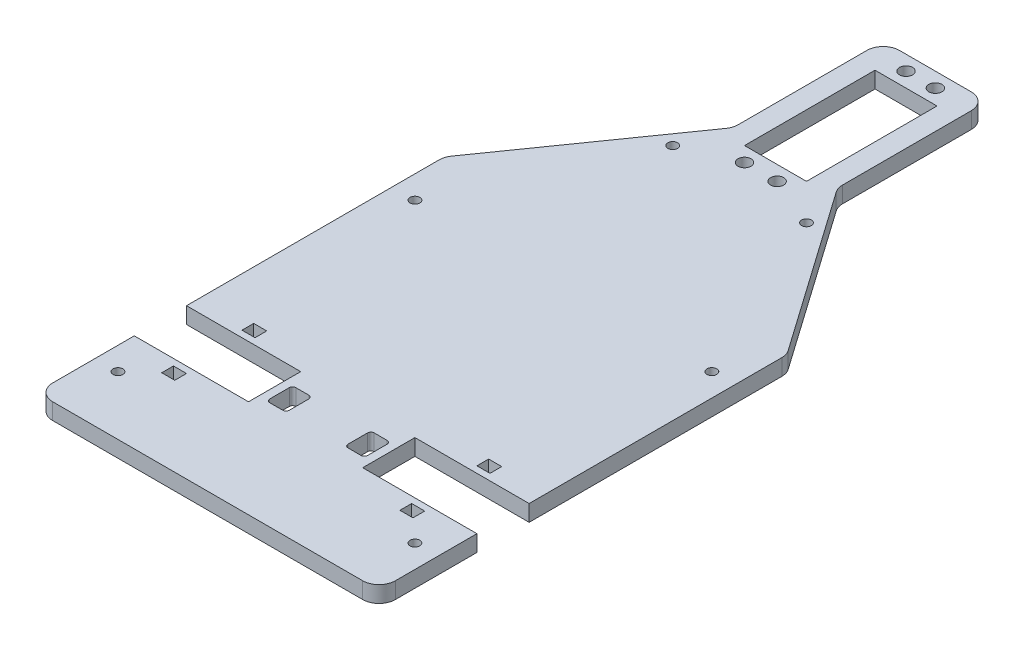
SolidWorks part; units mm, degrees
ref_plane "Front Plane" through (0, 0, 0) normal (0, 0, 1) x (1, 0, 0)
ref_plane "Top Plane" through (0, 0, 0) normal (0, 1, 0) x (1, 0, 0)
ref_plane "Right Plane" through (0, 0, 0) normal (1, 0, 0) x (0, 0, -1)
sketch "Sketch1" plane through (0, 0, 0) normal (0, 1, 0) x (1, 0, 0)
  line L0 (-16, 108) -> (16, 108)
  line L1 (16, 108) -> (16, 62)
  line L2 (16, 62) -> (52.5, 10)
  line L3 (52.5, 10) -> (52.5, -115)
  line L4 (52.5, -115) -> (-52.5, -115)
  line L5 (-52.5, -115) -> (-52.5, 10)
  line L6 (-52.5, 10) -> (-16, 62)
  line L7 (-16, 62) -> (-16, 108)
  dimension "D1" = 52.5
  dimension "D2" = 105
  dimension "D3" = 16
  dimension "D4" = 32
  dimension "D5" = 125
  dimension "D6" = 108
  dimension "D7" = 125
  dimension "D8" = 46
  dimension "D9" = 52
  dimension "D10" = 52
extrude "Boss-Extrude1" add sketch "Sketch1" along normal blind 5
sketch "Sketch2" plane through (0, 5, 0) normal (0, 1, 0) x (1, 0, 0)
  line L5 (-9.5, 59) -> (-9.5, 99)
  line L6 (-52.5, 10) -> (-52.5, -115) construction
  line L10 (-37.5, -63.4024) -> (-33.5042, -63.4024)
  line L11 (-37.5, -63.4024) -> (-37.5, -67)
  line L16 (52.5, 10) -> (52.5, -115) construction
  line L17 (-52.5, -69) -> (-17.5, -69)
  line L18 (-52.5, -115) -> (-52.5, 10) construction
  line L19 (-17.5, -69) -> (-17.5, -85)
  line L20 (-17.5, -85) -> (-52.5, -85)
  line L21 (-52.5, -85) -> (-52.5, -69)
  line L22 (17.5, -85) -> (17.5, -69)
  line L23 (17.5, -85) -> (52.5, -85)
  line L24 (17.5, -69) -> (52.5, -69)
  line L25 (52.5, -69) -> (52.5, -85)
  line L26 (-37.5, -67) -> (-33.5042, -67)
  line L27 (52.5, -115) -> (-52.5, -115) construction
  line L29 (-15, -82) -> (-9, -82)
  line L30 (-9, -82) -> (-9, -74)
  line L31 (-15, -74) -> (-9, -74)
  line L32 (-15, -82) -> (-15, -74)
  line L33 (9, -74) -> (9, -82)
  line L34 (9, -82) -> (15, -82)
  line L35 (15, -82) -> (15, -74)
  line L36 (15, -74) -> (9, -74)
  line L37 (-16, 108) -> (16, 108) construction
  line L38 (-16, 62) -> (-16, 108) construction
  line L39 (-33.5042, -63.4024) -> (-33.5042, -67)
  line L40 (-9.5, 99) -> (9.5, 99)
  line L41 (9.5, 99) -> (9.5, 59)
  line L42 (9.5, 59) -> (-9.5, 59)
  line L43 (-38.5, -87) -> (-34.5042, -87)
  line L44 (-38.5, -87) -> (-38.5, -90.6)
  line L45 (-38.5, -90.6) -> (-34.5042, -90.6)
  line L46 (-34.5042, -87) -> (-34.5042, -90.6)
  line L48 (34.5, -87) -> (38.5, -87)
  line L49 (34.5, -87) -> (34.5, -90.6)
  line L50 (34.5, -90.6) -> (38.5, -90.6)
  line L51 (38.5, -87) -> (38.5, -90.6)
  line L52 (34.5, -63.4) -> (38.5, -63.4)
  line L53 (34.5, -63.4) -> (34.5, -67)
  line L54 (34.5, -67) -> (38.5, -67)
  line L55 (38.5, -63.4) -> (38.5, -67)
  circle A0 centre (-4.5, 103.5) radius 2
  circle A1 centre (4.5, 103.5) radius 2
  circle A2 centre (-5, 54.5026) radius 2
  circle A3 centre (5, 54.5026) radius 2
  circle A6 centre (-20.5, 48) radius 1.5
  circle A7 centre (20.5, 48) radius 1.5
  circle A8 centre (45.5, -6) radius 1.5
  circle A9 centre (-45.5, -6) radius 1.5
  circle A10 centre (45.5, -97) radius 1.5
  circle A11 centre (-45.5, -97) radius 1.5
  point P20 (-37.5, -65.2012)
  point P73 (38.5, -65.2)
  dimension "D5" = 4
  dimension "D8" = 4
  dimension "D11" = 4
  dimension "D14" = 40
  dimension "D21" = 91
  dimension "D24" = 16
  dimension "D27" = 3
  dimension "D30" = 3
  dimension "D37" = 3
  dimension "D38" = 3
  dimension "D39" = 3
  dimension "D40" = 3
  dimension "D46" = 2
  dimension "D26" = 4
  dimension "D7" = 4.5
  dimension "D9" = 19
  dimension "D10" = 4.5
  dimension "D12" = 6.5
  dimension "D13" = 11
  dimension "D15" = 49
  dimension "D16" = 49
  dimension "D17" = 11
  dimension "D18" = 60
  dimension "D19" = 60
  dimension "D20" = 7
  dimension "D22" = 91
  dimension "D23" = 32
  dimension "D25" = 16
  dimension "D28" = 32
  dimension "D29" = 3.9958
  dimension "D31" = 3.5976
  dimension "D32" = 2
  dimension "D33" = 7
  dimension "D34" = 15
  dimension "D35" = 7
  dimension "D36" = 14
  dimension "D41" = 7
  dimension "D42" = 4.5
  dimension "D43" = 3.9958
  dimension "D44" = 5
  dimension "D45" = 5
  dimension "D47" = 3.6
  dimension "D48" = 3.6
  dimension "D49" = 35
  dimension "D50" = 16
  dimension "D51" = 30
  dimension "D52" = 16
  dimension "D53" = 35
  dimension "D54" = 30
  dimension "D55" = 8
  dimension "D56" = 6
  dimension "D57" = 2.5
  dimension "D58" = 5
  dimension "D59" = 8
  dimension "D60" = 6
  dimension "D61" = 2.5
  dimension "D62" = 5
  dimension "D63" = 4
  dimension "D64" = 2
  dimension "D65" = 14
  dimension "D66" = 14
  dimension "D67" = 4
  dimension "D68" = 3.6
  dimension "D69" = 2
extrude "Cut-Extrude1" cut sketch "Sketch2" against normal blind 7
fillet "Fillet1" radius 5 1 edges at (16, 2.5, -108)
fillet "Fillet2" radius 5 1 edges at (-16, 2.5, -108)
fillet "Fillet3" radius 5 1 edges at (52.5, 2.5, -10)
fillet "Fillet4" radius 5 1 edges at (-52.5, 2.5, -10)
fillet "Fillet5" radius 5 1 edges at (52.5, 2.5, 115)
fillet "Fillet6" radius 5 1 edges at (-52.5, 2.5, 115)
fillet "Fillet8" radius 1 1 edges at (15, 2.5, 74)
fillet "Fillet9" radius 1 7 edges at (-15, 2.5, 82) (-15, 2.5, 74) (-9, 2.5, 82) (-9, 2.5, 74) (9, 2.5, 82) (15, 2.5, 82) (9, 2.5, 74)
fillet "Fillet10" radius 5 2 edges at (-16, 2.5, -62) (16, 2.5, -62)
